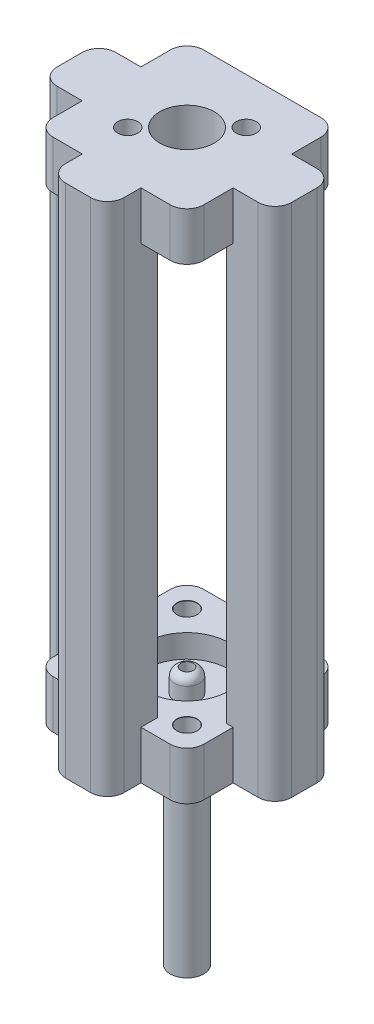
SolidWorks part; units mm, degrees
ref_plane "Front Plane" through (0, 0, 0) normal (0, 0, 1) x (1, 0, 0)
ref_plane "Top Plane" through (0, 0, 0) normal (0, 1, 0) x (1, 0, 0)
ref_plane "Right Plane" through (0, 0, 0) normal (1, 0, 0) x (0, 0, -1)
sketch "Sketch1" plane through (0, 0, 0) normal (0, 1, 0) x (1, 0, 0)
  line L1 (-9, -9) -> (9, -9)
  line L2 (-9, -9) -> (-9, 9)
  line L3 (-9, 9) -> (9, 9)
  line L4 (9, -9) -> (9, 9)
  line L5 (-9, -9) -> (9, 9) construction
  line L6 (-9, 9) -> (9, -9) construction
  point P0 (0, 0)
  dimension "D1" = 18
  dimension "D2" = 18
extrude "Boss-Extrude1" add sketch "Sketch1" along normal blind 5.75
sketch "Sketch2" plane through (0, 5.75, 0) normal (0, 1, 0) x (1, 0, 0)
  line L0 (0, 9) -> (0, -9) construction
  line L1 (9, 9) -> (-9, 9) construction
  line L2 (-9, -9) -> (9, -9) construction
  line L3 (-9, 0) -> (9, 0) construction
  line L4 (-9, 9) -> (-9, -9) construction
  line L5 (9, -9) -> (9, 9) construction
  line L6 (-9, 9) -> (9, -9) construction
  line L7 (-9, -9) -> (9, 9) construction
hole_wizard "M2 Clearance Hole1" positions "Sketch3" profile "Sketch4" hole size "M2" standard "ANSI Metric" end condition up to next
sketch "Sketch3" plane through (0, 5.75, 0) normal (0, 1, 0) x (1, 0, 0)
  line L0 (-9, 9) -> (9, -9) construction
  line L1 (-9, -9) -> (9, 9) construction
  point P0 (-6, 6)
  point P4 (6, 6)
  point P8 (-6, -6)
  point P10 (6, -6)
  dimension "D1" = 12
  dimension "D2" = 12
sketch "Sketch4" plane through (-6, 5.75, -6) normal (1, 0, 0) x (0, 0, 1)
  line L0 (0, 0) -> (0, 5.75)
  line L1 (0, 5.75) -> (1.2, 5.75)
  line L2 (1.2, 5.75) -> (1.2, 0.025)
  line L3 (1.2, 0.025) -> (1.225, 0)
  line L5 (1.225, 0) -> (0, 0)
  line L6 (-1.2, 0.025) -> (-1.225, 0) construction
  line L11 (0, -6.35) -> (0, 107.95) construction
  dimension "Thru Hole Dia." = 2.4
  dimension "Thru Hole Depth" = 5.75
  dimension "Near C'Sink Dia." = 2.45
  dimension "Near C'Sink Angle" = 90
sketch "Sketch5" plane through (0, 5.75, 0) normal (0, 1, 0) x (1, 0, 0)
  line L0 (0, -13) -> (0, -7) construction
  line L1 (-14, -3.5) -> (-8.2, -3.5)
  line L2 (-14, -3.5) -> (-14, 3.5)
  line L3 (-14, 3.5) -> (-8.2, 3.5)
  line L4 (-8.2, -3.5) -> (-8.2, 3.5)
  line L5 (9, 0) -> (-9, 0) construction
  line L6 (9, -9) -> (9, 9) construction
  line L11 (8.2, 3.5) -> (8.2, -3.5)
  line L12 (14, -3.5) -> (8.2, -3.5)
  line L13 (14, 3.5) -> (14, -3.5)
  line L14 (14, 3.5) -> (8.2, 3.5)
  line L15 (3.5, -7) -> (1.5, -7)
  line L16 (-3.5, -9) -> (-3.5, -7)
  line L17 (3.5, -9) -> (0, -9) construction
  line L18 (3.5, -9) -> (3.5, -7)
  line L19 (0, 9) -> (0, -9) construction
  line L20 (9, 9) -> (-9, 9) construction
  line L21 (-1.5, -7) -> (-1.5, -7.5)
  line L22 (-1.5, -7.5) -> (1.5, -7.5)
  line L23 (1.5, -7) -> (1.5, -7.5)
  line L24 (-9, -9) -> (9, -9) construction
  line L25 (0, -7) -> (-1.5, -7) construction
  line L26 (-1.5, -7) -> (-3.5, -7)
  line L27 (1.5, -7) -> (0, -7) construction
  line L31 (-9, 3.5) -> (-9, -3.5) construction
  line L32 (-9, 9) -> (-9, -9) construction
  line L33 (9, 3.5) -> (9, -3.5) construction
  line L34 (-3.5, -9) -> (-3.5, -13)
  line L35 (-3.5, -13) -> (3.5, -13)
  line L36 (3.5, -13) -> (3.5, -9)
  line L37 (0, -9) -> (-3.5, -9) construction
  point P11 (-14, 0)
  point P27 (0, 0)
  point P32 (0, -7.5)
  dimension "D1" = 0.8
  dimension "D2" = 7
  dimension "D3" = 0.8
  dimension "D4" = 7
  dimension "D5" = 2
  dimension "D6" = 7
  dimension "D7" = 3.5
  dimension "D8" = 0.5
  dimension "D9" = 3
  dimension "D10" = 5
  dimension "D11" = 5
  dimension "D12" = 4
extrude "Boss-Extrude2" add sketch "Sketch5" along normal blind 50
sketch "Sketch6" plane through (0, 5.75, 0) normal (0, 1, 0) x (1, 0, 0)
  circle A0 centre (0, 0) radius 4.0625
  dimension "D1" = 8.125
extrude "Cut-Extrude1" cut sketch "Sketch6" against normal up to surface (5.75 mm away) up to face at (-6, 0, -7.2)
ref_plane "Plane1" through (0, 30.75, 0) normal (0, 1, 0) x (1, 0, 0)
mirror "Mirror1" about plane through (0, 30.75, 0) normal (0, 1, 0) of "Boss-Extrude1"
sketch "Sketch7" plane through (0, 61.5, 0) normal (0, 1, 0) x (1, 0, 0)
  line L0 (-5, 9) -> (-5, -9) construction
  line L1 (9, 9) -> (-9, 9) construction
  line L2 (-9, -9) -> (9, -9) construction
  line L3 (5, 9) -> (5, -9) construction
  line L4 (-9, 0) -> (9, 0) construction
  line L5 (-9, 9) -> (-9, -9) construction
  line L6 (9, -9) -> (9, 9) construction
  line L7 (-9, 9) -> (9, -9) construction
  line L8 (-9, -9) -> (9, 9) construction
  circle A0 centre (0, 0) radius 3.25
  circle A1 centre (-5, 0) radius 1 construction
  circle A2 centre (5, 0) radius 1 construction
  dimension "D3" = 6.5
  dimension "D4" = 2
  dimension "D1" = 5
  dimension "D2" = 5
extrude "Cut-Extrude2" cut sketch "Sketch7" against normal up to surface (5.75 mm away) up to face at (0, 55.75, 3.05)
fillet "Fillet1" radius 2 8 edges at (9, 2.875, -9) (-9, 2.875, -9) (-9, 2.875, 9) (9, 2.875, 9) (9, 58.625, -9) (-9, 58.625, -9) (9, 58.625, 9) (-9, 58.625, 9)
hole_wizard "M2 Clearance Hole2" positions "Sketch8" profile "Sketch10" hole size "M2" standard "ANSI Metric"
sketch "Sketch8" plane through (0, 61.5, 0) normal (0, 1, 0) x (1, 0, 0)
  line L1 (-9, -9) -> (9, 9) construction
  point P7 (-3.5355, -3.5355)
  point P11 (3.5355, 3.5355)
  dimension "D1" = 5
  dimension "D2" = 5
sketch "Sketch10" plane through (-3.5355, 61.5, 3.5355) normal (1, 0, 0) x (0, 0, 1)
  line L0 (0, 0) -> (0, 6.471)
  line L1 (0, 6.471) -> (1.2, 5.75)
  line L2 (1.2, 5.75) -> (1.2, 0)
  line L5 (1.2, 0) -> (0, 0)
  line L10 (0, 6.471) -> (-1.2, 5.75) construction
  line L11 (0, -6.35) -> (0, 107.95) construction
  dimension "Hole Dia." = 2.4
  dimension "Hole Depth" = 5.75
  dimension "Drill Angle" = 118
sketch "Sketch11" plane through (0, 55.75, 0) normal (0, 1, 0) x (1, 0, 0)
  line L0 (-7, -9) -> (7, -9) construction
  line L1 (-14, -3.5) -> (-9, -3.5)
  line L2 (-14, -3.5) -> (-14, 3.5)
  line L3 (-14, 3.5) -> (-9, 3.5)
  line L4 (-9, -3.5) -> (-9, 3.5)
  line L5 (14, -3.5) -> (9, -3.5)
  line L6 (14, -3.5) -> (14, 3.5)
  line L7 (14, 3.5) -> (9, 3.5)
  line L8 (9, -3.5) -> (9, 3.5)
  line L9 (3.5, -13) -> (-3.5, -13)
  line L10 (3.5, -13) -> (3.5, -9)
  line L11 (3.5, -9) -> (-3.5, -9)
  line L12 (-3.5, -13) -> (-3.5, -9)
  line L13 (-3.5, -9) -> (3.5, -9) construction
extrude "Boss-Extrude3" add sketch "Sketch11" along normal up to surface (5.75 mm away) up to face at (-3.5355, 61.5, 4.7355)
sketch "Sketch12" plane through (0, 5.75, 0) normal (0, -1, 0) x (1, 0, 0)
  line L0 (-9, -7) -> (-9, 7) construction
  line L1 (-14, -3.5) -> (-9, -3.5)
  line L2 (-14, -3.5) -> (-14, 3.5)
  line L3 (-14, 3.5) -> (-9, 3.5)
  line L4 (-9, -3.5) -> (-9, 3.5)
  line L5 (-9, -3.5) -> (-9, 3.5) construction
  line L6 (-14, 3.5) -> (-9, 3.5) construction
  line L7 (-3.5, 13) -> (3.5, 13)
  line L8 (-3.5, 13) -> (-3.5, 9)
  line L9 (-3.5, 9) -> (3.5, 9)
  line L10 (3.5, 13) -> (3.5, 9)
  line L11 (14, -3.5) -> (9, -3.5)
  line L12 (14, -3.5) -> (14, 3.5)
  line L13 (14, 3.5) -> (9, 3.5)
  line L14 (9, -3.5) -> (9, 3.5)
extrude "Boss-Extrude4" add sketch "Sketch12" along normal up to surface (5.75 mm away) up to face at (0, 0, -4.0625)
fillet "Fillet2" radius 2 6 edges at (-14, 30.75, -3.5) (-14, 30.75, 3.5) (3.5, 30.75, 13) (-3.5, 30.75, 13) (14, 30.75, 3.5) (14, 30.75, -3.5)
sketch "Sketch13" plane through (-8.2, 0, 0) normal (1, 0, 0) x (0, 0, -1)
  line L0 (3.5, 55.75) -> (3.5, 5.75) construction
  line L1 (3.5, 5.75) -> (-3.5, 5.75)
  line L2 (3.5, 5.75) -> (3.5, 38.75)
  line L3 (3.5, 38.75) -> (-3.5, 38.75)
  line L4 (-3.5, 5.75) -> (-3.5, 38.75)
  line L5 (-3.5, 55.75) -> (-3.5, 5.75) construction
  line L7 (-3.5, 55.75) -> (3.5, 55.75) construction
  line L8 (3.5, 5.75) -> (7, 5.75) construction
  dimension "D2" = 17
ref_plane "Plane2" through (0, 0, 0) normal (1, 0, 0) x (0, 0, -1)
ref_plane "Plane3" through (0, 5.75, 0) normal (0, 1, 0) x (1, 0, 0)
sketch "Sketch15" plane through (0, 5.75, 0) normal (0, 1, 0) x (1, 0, 0)
  circle A0 centre (0, 0) radius 4.0625
  circle A1 centre (0, 0) radius 4.0625 construction
  circle A2 centre (0, 0) radius 0.75
  dimension "D1" = 1.5
extrude "Boss-Extrude5" add sketch "Sketch15" against normal up to surface (5.75 mm away) up to face at (0, 0, -4.0625)
sketch "Sketch16" plane through (0, 0, 0) normal (0, -1, 0) x (1, 0, 0)
  circle A0 centre (0, 0) radius 0.75
  circle A1 centre (0, 0) radius 2
  circle A2 centre (0, 0) radius 0.75 construction
  dimension "D1" = 4
extrude "Boss-Extrude6" add sketch "Sketch16" along normal blind 25
sketch "Sketch17" plane through (0, 5.75, 0) normal (0, 1, 0) x (1, 0, 0)
  circle A0 centre (0, 0) radius 5
  circle A1 centre (0, 0) radius 1.5
  circle A2 centre (0, 0) radius 2
  circle M30 centre (0, 0) radius 0.75
  dimension "D1" = 10
  dimension "D2" = 3
  dimension "D3" = 4
extrude "Cut-Extrude3" cut sketch "Sketch17" against normal blind 2.75 contours A0 A1 | A2 M30 region at (-4.8586, 5.75, 0) region at (-1.9434, 5.75, 0)
ref_plane "Plane4" through (0, 0, -0.75) normal (0, 0, 1) x (1, 0, 0)
ref_plane "Plane5" through (0, 0, 0) normal (0, 0, 1) x (1, 0, 0)
sketch "Sketch19" plane through (0, 0, 0) normal (0, 0, 1) x (1, 0, 0)
  line L0 (0, -25) -> (-1.5, -25)
  line L1 (-1.5, -25) -> (0, -15)
  line L2 (0, -15) -> (0, -25)
  line L3 (-2, -25) -> (2, -25) construction
  line L4 (-0.75, -25) -> (0.75, -25) construction
  dimension "D1" = 10
  dimension "D2" = 1.5
revolve "Cut-Revolve1" cut sketch "Sketch19" angle 360 about L2
chamfer "Chamfer1" distance 0.25 angle 45 1 edges at (-1.5, -25, 0) first distance on face at (-1.5, -25, 0)
fillet "Fillet3" radius 1 1 edges at (0, 5.75, 1.5)
